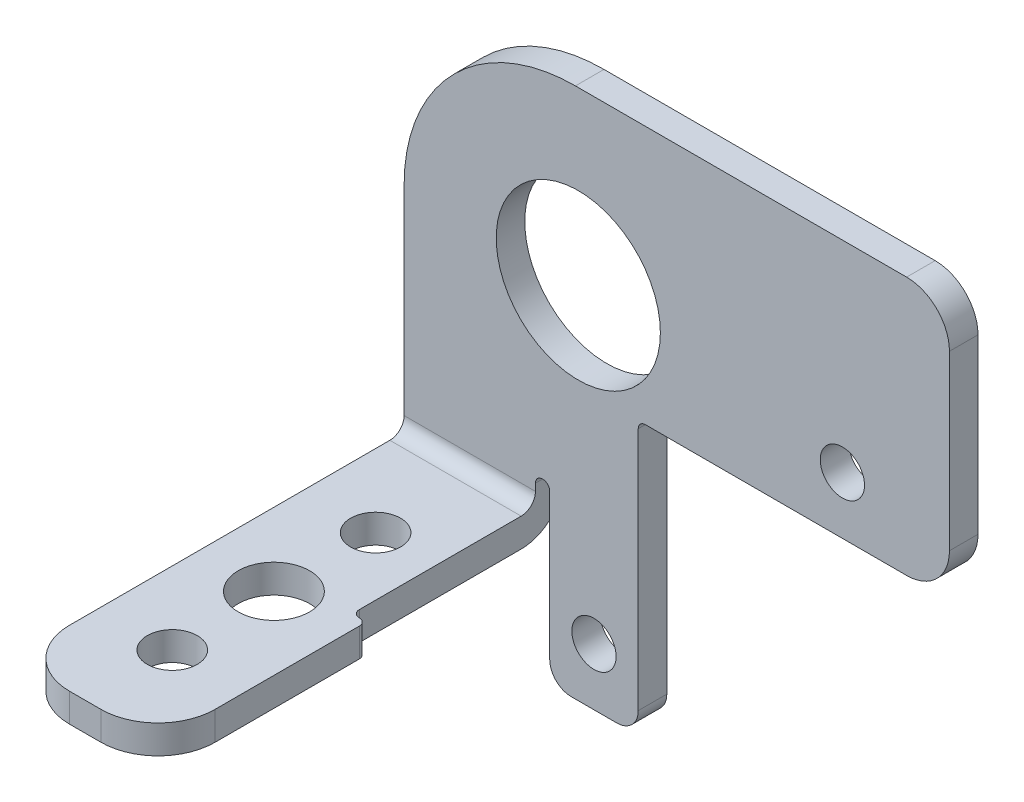
SolidWorks part; units mm, degrees
material "1023 Carbon Steel Sheet (SS)"
ref_plane "Front Plane" through (0, 0, 0) normal (0, 0, 1) x (1, 0, 0)
ref_plane "Top Plane" through (0, 0, 0) normal (0, 1, 0) x (1, 0, 0)
ref_plane "Right Plane" through (0, 0, 0) normal (1, 0, 0) x (0, 0, -1)
sketch "Sketch1" plane through (0, 0, 0) normal (0, 0, 1) x (1, 0, 0)
  line L0 (0, 0) -> (-38.2, 0)
  line L1 (-38.2, 0) -> (-38.2, -26)
  line L2 (-38.2, -26) -> (-29, -26)
  line L3 (-29, -26) -> (-29, -25)
  line L4 (-29, -25) -> (-28, -25)
  line L5 (-28, -25) -> (-28, -37.2)
  line L6 (-28, -37.2) -> (-21.8, -37.2)
  line L7 (-21.8, -37.2) -> (-21.8, -18.1)
  line L8 (-21.8, -18.1) -> (0, -18.1)
  line L9 (0, -18.1) -> (0, 0)
  dimension "D1" = 18.1
  dimension "D2" = 38.2
  dimension "D3" = 21.8
  dimension "D4" = 19.1
  dimension "D5" = 6.2
  dimension "D6" = 12.2
  dimension "D7" = 1
  dimension "D8" = 1
extrude "Boss-Extrude1" add sketch "Sketch1" along normal blind 2
sketch "Sketch2" plane through (-38.2, 0, 0) normal (-1, 0, 0) x (0, 0, 1)
  line L0 (3, -27) -> (11.0253, -27) construction
  line L1 (2, 0) -> (2, -26) construction
  line L2 (0, -26) -> (2, -26)
  line L3 (3, -27) -> (3, -29)
  arc A0 (2, -26) -> (3, -27) centre (3, -26) ccw
  arc A1 (0, -26) -> (3, -29) centre (3, -26) ccw
  dimension "D1" = 1
extrude "Boss-Extrude2" add sketch "Sketch2" against normal up to surface (9.2 mm away) up to face at (-29, -25.5, 1)
sketch "Sketch3" plane through (0, 0, 3) normal (0, 0, 1) x (1, 0, 0)
  line L1 (-38.2, -27) -> (-29, -27)
  line L2 (-38.2, -27) -> (-38.2, -29)
  line L3 (-38.2, -29) -> (-29, -29)
  line L4 (-29, -27) -> (-29, -29)
extrude "Boss-Extrude3" add sketch "Sketch3" along normal blind 11.84
sketch "Sketch4" plane through (0, -27, 0) normal (0, 1, 0) x (1, 0, 0)
  line L0 (-29, -14.84) -> (-29, -3) construction
  line L1 (-38.2, -14.84) -> (-28, -14.84)
  line L2 (-38.2, -14.84) -> (-38.2, -29.44)
  line L3 (-38.2, -29.44) -> (-28, -29.44)
  line L4 (-28, -14.84) -> (-28, -29.44)
  dimension "D1" = 1
  dimension "D2" = 14.6
extrude "Boss-Extrude4" add sketch "Sketch4" against normal up to surface (2 mm away) up to face at (-33.6, -29, 8.92)
fillet "Fillet1" radius 3 2 edges at (0, -18.1, 1) (0, 0, 1)
fillet "Fillet2" radius 12 1 edges at (-38.2, 0, 1)
sketch "Sketch5" plane through (0, 0, 2) normal (0, 0, 1) x (1, 0, 0)
  line L0 (-28, -37.2) -> (-21.8, -37.2) construction
  line L1 (-21.8, -18.1) -> (-3, -18.1) construction
  line L2 (0, -15.1) -> (0, -3) construction
  circle A0 centre (-7.5, -14.1) radius 1.55
  circle A1 centre (-24.9, -33.2) radius 1.55
  point P6 (-24.9, -37.2)
  dimension "D1" = 3.1
  dimension "D2" = 3.1
  dimension "D3" = 4
  dimension "D4" = 7.5
  dimension "D5" = 4
extrude "Cut-Extrude1" cut sketch "Sketch5" against normal through all
fillet "Fillet3" radius 1.5 2 edges at (-28, -37.2, 1) (-21.8, -37.2, 1)
fillet "Fillet4" radius 0.5 2 edges at (-28, -25, 1) (-29, -25, 1)
fillet "Fillet5" radius 0.5 2 edges at (-28, -28, 14.84) (-29, -28, 14.84)
fillet "Fillet6" radius 4 2 edges at (-38.2, -28, 29.44) (-28, -28, 29.44)
fillet "Fillet7" radius 0.5 1 edges at (-21.8, -18.1, 1)
sketch "Sketch6" plane through (0, 0, 2) normal (0, 0, 1) x (1, 0, 0)
  line L0 (0, -15.1) -> (0, -3) construction
  line L1 (-3, 0) -> (-26.2, 0) construction
  circle A0 centre (-26, -12) radius 5.75
  dimension "D1" = 11.5
  dimension "D2" = 26
  dimension "D3" = 12
extrude "Cut-Extrude2" cut sketch "Sketch6" against normal through all
sketch "Sketch7" plane through (0, -27, 0) normal (0, 1, 0) x (1, 0, 0)
  line L0 (-33.1, -23.3422) -> (-33.1, -9.0978) construction
  line L1 (-32, -29.44) -> (-32, -3) construction
  line L2 (-29, -3) -> (-38.2, -3) construction
  line L3 (-34.2, -29.44) -> (-32, -29.44) construction
  circle A0 centre (-33.1, -23.3422) radius 1.75
  circle A1 centre (-33.1, -9.0978) radius 1.75
  circle A2 centre (-33.1, -16.22) radius 2.5
  point P9 (-32, -16.22)
  point P10 (-33.1, -16.22)
  point P13 (-33.1, -29.44)
  dimension "D1" = 3.5
  dimension "D2" = 3.5
  dimension "D3" = 5
extrude "Cut-Extrude3" cut sketch "Sketch7" against normal through all
